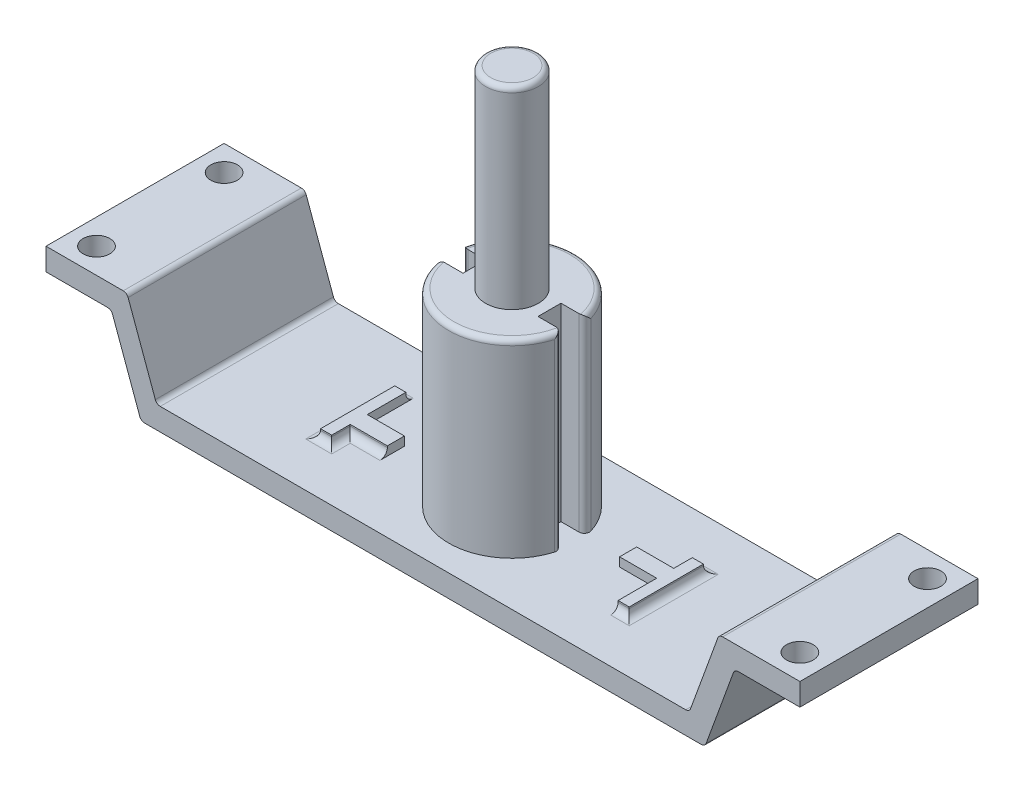
SolidWorks part; units mm, degrees
ref_plane "Front Plane" through (0, 0, 0) normal (0, 0, 1) x (1, 0, 0)
ref_plane "Top Plane" through (0, 0, 0) normal (0, 1, 0) x (1, 0, 0)
ref_plane "Right Plane" through (0, 0, 0) normal (1, 0, 0) x (0, 0, -1)
sketch "Sketch1" plane through (0, 0, 0) normal (0, 1, 0) x (1, 0, 0)
  line L1 (-38, 12) -> (38, 12)
  line L2 (-38, 12) -> (-38, -12)
  line L3 (-38, -12) -> (38, -12)
  line L4 (38, 12) -> (38, -12)
  line L5 (-38, 12) -> (38, -12) construction
  line L6 (-38, -12) -> (38, 12) construction
  point P0 (0, 0)
  dimension "D1" = 24
  dimension "D2" = 76
extrude "Boss-Extrude1" add sketch "Sketch1" along normal blind 3
sketch "Sketch2" plane through (0, 0, 12) normal (0, 0, 1) x (1, 0, 0)
  line L0 (-38, 0) -> (-42.0037, 11)
  line L1 (-42.0037, 11) -> (-50.8037, 11)
  line L2 (-50.8037, 11) -> (-50.8037, 14)
  line L3 (-50.8037, 14) -> (-39.903, 14)
  line L4 (-39.903, 14) -> (-35.8994, 3)
  line L5 (-38, 3) -> (38, 3) construction
  line L6 (-38, 0) -> (38, 0) construction
  line L7 (-38, 0) -> (-35.8994, 3)
  line L9 (0, -55) -> (0, 55) construction
  line L10 (38, 0) -> (42.0037, 11)
  line L11 (42.0037, 11) -> (50.8037, 11)
  line L12 (50.8037, 11) -> (50.8037, 14)
  line L13 (50.8037, 14) -> (39.903, 14)
  line L14 (39.903, 14) -> (35.8994, 3)
  line L15 (38, 0) -> (35.8994, 3)
  dimension "D1" = 8.8
  dimension "D2" = 3
  dimension "D3" = 3
  dimension "D4" = 11
  dimension "D5" = 70
extrude "Boss-Extrude2" add sketch "Sketch2" against normal blind 24
sketch "Sketch3" plane through (0, 3, 0) normal (0, 1, 0) x (1, 0, 0)
  circle A0 centre (0, 0) radius 8.525
  dimension "D1" = 17.05
extrude "Boss-Extrude3" add sketch "Sketch3" along normal blind 25.5
sketch "Sketch4" plane through (0, 28.5, 0) normal (0, 1, 0) x (1, 0, 0)
  circle A0 centre (0, 0) radius 3.55
  dimension "D1" = 7.1
extrude "Boss-Extrude4" add sketch "Sketch4" along normal blind 26
sketch "Sketch5" plane through (0, 28.5, 0) normal (0, 1, 0) x (1, 0, 0)
  line L0 (0, -55) -> (0, 55) construction
  line L1 (-9.05, 1.55) -> (-5.05, 1.55)
  line L2 (-9.05, 1.55) -> (-9.05, -1.55)
  line L3 (-9.05, -1.55) -> (-5.05, -1.55)
  line L4 (-5.05, 1.55) -> (-5.05, -1.55)
  line L5 (-9.05, 1.55) -> (-5.05, -1.55) construction
  line L6 (-9.05, -1.55) -> (-5.05, 1.55) construction
  line L7 (9.05, -1.55) -> (5.05, -1.55)
  line L8 (5.05, 1.55) -> (5.05, -1.55)
  line L9 (9.05, 1.55) -> (5.05, 1.55)
  line L10 (9.05, 1.55) -> (9.05, -1.55)
  point P0 (-7.05, 0)
  dimension "D1" = 3.1
  dimension "D2" = 5.05
  dimension "D3" = 4
extrude "Cut-Extrude1" cut sketch "Sketch5" against normal up to surface (25.5 mm away) up to face at (0, 3, 8.525)
sketch "Sketch6" plane through (0, 14, 0) normal (0, 1, 0) x (1, 0, 0)
  line L0 (-55, 0) -> (55, 0) construction
  line L3 (0, -55) -> (0, 55) construction
  circle A0 centre (-47.4, 8.6) radius 1.8
  circle A1 centre (-47.4, -8.6) radius 1.8
  circle A2 centre (47.4, -8.6) radius 1.8
  circle A3 centre (47.4, 8.6) radius 1.8
  dimension "D1" = 3.6
  dimension "D2" = 8.6
  dimension "D3" = 47.4
extrude "Cut-Extrude2" cut sketch "Sketch6" against normal up to next
sketch "Sketch7" plane through (0, 3, 0) normal (0, 1, 0) x (1, 0, 0)
  line L0 (-19.3, -2.5) -> (-19.3, -5)
  line L1 (-20.8, 5) -> (-19.3, 5)
  line L2 (-20.8, 5) -> (-20.8, -5)
  line L3 (-20.8, -5) -> (-19.3, -5)
  line L4 (20.8, 5) -> (20.8, -5)
  line L5 (19.3, 0.2) -> (14.3, 0.2)
  line L6 (-19.3, -0.2) -> (-14.3, -0.2)
  line L7 (19.3, -5) -> (20.8, -5)
  line L9 (-19.3, 5) -> (-19.3, -0.2)
  line L11 (19.3, 5) -> (19.3, 2.5)
  line L13 (-19.3, -2.5) -> (-14.3, -2.5)
  line L14 (-14.3, -0.2) -> (-14.3, -2.5)
  line L16 (19.3, 5) -> (20.8, 5)
  line L17 (19.3, 2.5) -> (14.3, 2.5)
  line L18 (14.3, 0.2) -> (14.3, 2.5)
  line L19 (19.3, 0.2) -> (19.3, -5)
  point P0 (0, 0)
  point P8 (0, 0)
  point P16 (-19.3, 0.5145)
  point P17 (-19.3, -0.6887)
  point P22 (19.3, 0.2163)
  point P23 (19.3, 0.8287)
  dimension "D1" = 41.6
  dimension "D2" = 38.6
  dimension "D3" = 10
  dimension "D4" = 5
  dimension "D5" = 2.3
  dimension "D6" = 19.3
  dimension "D9" = 5
  dimension "D10" = 2.3
  dimension "D7" = 0.2
  dimension "D8" = 0.2
extrude "Boss-Extrude5" add sketch "Sketch7" along normal blind 1.2
fillet "Fillet1" radius 1 10 edges at (20.05, 3, -5) (20.8, 3, 0) (20.05, 3, 5) (-20.05, 3, -5) (-20.05, 3, 5) (-20.8, 3, 0) (19.3, 3, -3.75) (16.8, 3, -2.5) (-16.8, 3, 2.5) (-19.3, 3, 3.75)
fillet "Fillet2" radius 0.7 15 edges at (0, 54.5, 3.55) (42.0037, 11, 0) (38, 0, 0) (-38, 0, 0) (-42.0037, 11, 0) (39.903, 14, 0) (35.8994, 3, 0) (-35.8994, 3, 0) (-39.903, 14, 0) (8.3829, 15.75, 1.55) (8.3829, 15.75, -1.55) (-8.3829, 15.75, 1.55) (-8.3829, 15.75, -1.55) (0, 28.5, -8.525) (0, 28.5, 8.525)
equation "\"D6@Sketch7\"=\"D2@Sketch7\"/2"
equation "\"D9@Sketch7\"=\"D4@Sketch7\""
equation "\"D10@Sketch7\"=\"D5@Sketch7\""
equation "\"D8@Sketch7\"=\"D7@Sketch7\""
